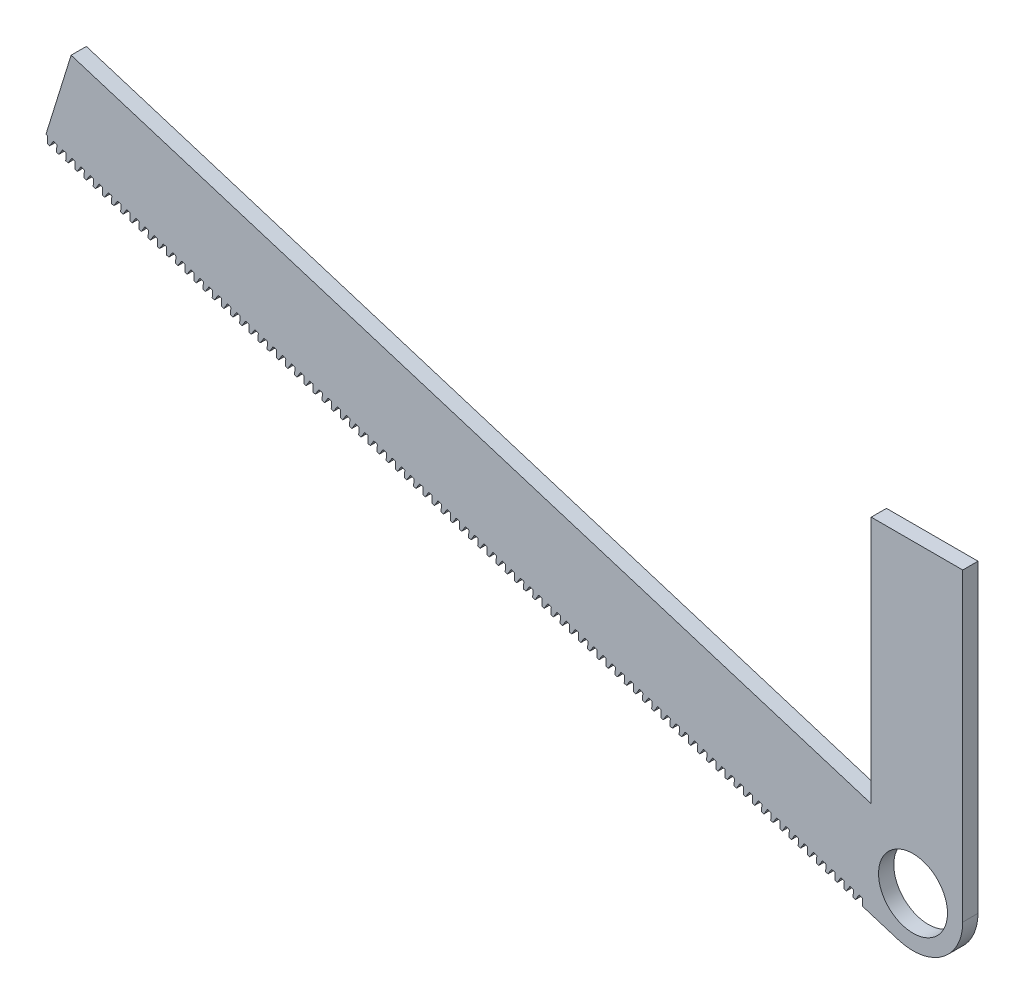
SolidWorks part; units mm, degrees
material "6061-T6 (SS)"
ref_plane "Front Plane" through (0, 0, 0) normal (0, 0, 1) x (1, 0, 0)
ref_plane "Top Plane" through (0, 0, 0) normal (0, 1, 0) x (1, 0, 0)
ref_plane "Right Plane" through (0, 0, 0) normal (1, 0, 0) x (0, 0, -1)
sketch "Sketch1" plane through (0, 0, 0) normal (0, 0, 1) x (1, 0, 0)
  line L0 (19.05, 0) -> (19.05, -76.2) construction
  line L1 (0, 19.05) -> (-57.15, 19.05) construction
  line L2 (19.05, -155.575) -> (168.9894, -155.575) construction
  line L3 (0, -95.25) -> (-57.15, -95.25) construction
  line L4 (-57.15, -95.25) -> (-57.15, 19.05) construction
  line L5 (168.9894, 7.239) -> (168.9894, -18.161) construction
  line L6 (168.9894, -18.161) -> (168.9894, -155.575) construction
  line L7 (168.9894, 7.239) -> (143.6189, 6.0141) construction
  line L8 (143.6189, 6.0141) -> (19.05, 0) construction
  line L9 (162.8555, -12.5324) -> (-192.7445, 97.7886)
  line L10 (189.6904, 7.239) -> (189.6904, 134.1777)
  line L12 (194.3894, 7.239) -> (194.3894, 143.2566) construction
  line L13 (189.6904, 134.1777) -> (151.5904, 134.1777)
  line L14 (151.5904, 134.1777) -> (151.5904, 30.8539)
  line L15 (151.5904, 30.8539) -> (-181.4552, 134.1777)
  line L16 (-181.4552, 134.1777) -> (-192.7445, 97.7886)
  line L17 (151.5904, 134.1777) -> (-181.4552, 134.1777) construction
  arc A0 (19.05, 0) -> (0, 19.05) centre (0, 0) ccw construction
  arc A1 (19.05, -76.2) -> (0, -95.25) centre (0, -76.2) cw construction
  circle A2 centre (168.9894, 7.239) radius 14.351
  circle A3 centre (168.9894, 7.239) radius 25.4 construction
  arc A4 (162.8555, -12.5324) -> (189.6904, 7.239) centre (168.9894, 7.239) ccw
  dimension "D1" = 19.05
  dimension "D4" = 19.05
  dimension "D6" = 28.702
  dimension "D7" = 50.8
  dimension "D10" = 6.35
  dimension "D13" = 251.5394
  dimension "D2" = 155.575
  dimension "D3" = 76.2
  dimension "D5" = 114.3
  dimension "D8" = 137.414
  dimension "D9" = 124.714
  dimension "D11" = 20
  dimension "D12" = 355.6
  dimension "D14" = 38.1
  dimension "D15" = 38.1
extrude "Boss-Extrude1" add sketch "Sketch1" along normal blind 6.35
sketch "Sketch2" plane through (0, 0, 6.35) normal (0, 0, 1) x (1, 0, 0)
  line L0 (-191.3232, 97.4142) -> (-191.1986, 100.0218)
  line L1 (-191.4127, 100.3274) -> (-192.4055, 100.6354)
  line L2 (-192.755, 100.5046) -> (-194.1282, 98.2844)
  line L3 (-194.194, 98.2383) -> (-194.1865, 98.2626) construction
  line L4 (-191.9091, 100.4814) -> (-192.7445, 97.7886) construction
  line L5 (-191.2875, 98.6929) -> (-193.4338, 99.3588) construction
  line L6 (-192.7445, 97.7886) -> (162.8555, -12.5324) construction
  line L7 (-193.4589, 99.3666) -> (-193.9484, 97.7886) construction
  line L8 (-191.2624, 98.6852) -> (-191.5406, 97.7886) construction
  line L11 (-191.295, 97.339) -> (-194.194, 98.2383)
  line L12 (-181.4552, 134.1777) -> (-192.7445, 97.7886) construction
  line L13 (-191.2875, 97.3632) -> (-190.8314, 97.2217)
  line L14 (-190.8314, 97.2217) -> (-190.8389, 97.1975)
  line L15 (-190.8389, 97.1975) -> (-191.295, 97.339)
  line L16 (-191.295, 97.339) -> (-191.2875, 97.3632) construction
  line L17 (-194.6425, 98.4041) -> (-194.6501, 98.3798)
  line L18 (-194.6501, 98.3798) -> (-194.194, 98.2383)
  line L19 (-194.1865, 98.2626) -> (-194.6425, 98.4041)
  arc A0 (-192.4055, 100.6354) -> (-192.755, 100.5046) centre (-192.4958, 100.3443) ccw
  arc A1 (-191.1986, 100.0218) -> (-191.4127, 100.3274) centre (-191.503, 100.0363) ccw
  arc A2 (-194.1865, 98.2626) -> (-194.1282, 98.2844) centre (-194.1714, 98.3111) ccw
  arc A3 (-191.3232, 97.4142) -> (-191.2875, 97.3632) centre (-191.2724, 97.4117) ccw
  point P6 (-192.3607, 99.0259)
  dimension "D1" = 0.0254
  dimension "Root_fillet" = 0.3048
  dimension "Break_rad" = 0.0508
  dimension "Gap_width" = 2.2997
  dimension "Dedendum" = 1.524
  dimension "Addendum_plus" = 1.2954
  dimension "Pressure_angle" = 14.5
  dimension "D2" = 0.4775
extrude "Cut-Extrude2" cut sketch "Sketch2" against normal through all
pattern_linear "LPattern2" count 90 spacing 3.9903 along (0.9551, -0.2963, 0) of "Cut-Extrude2"
